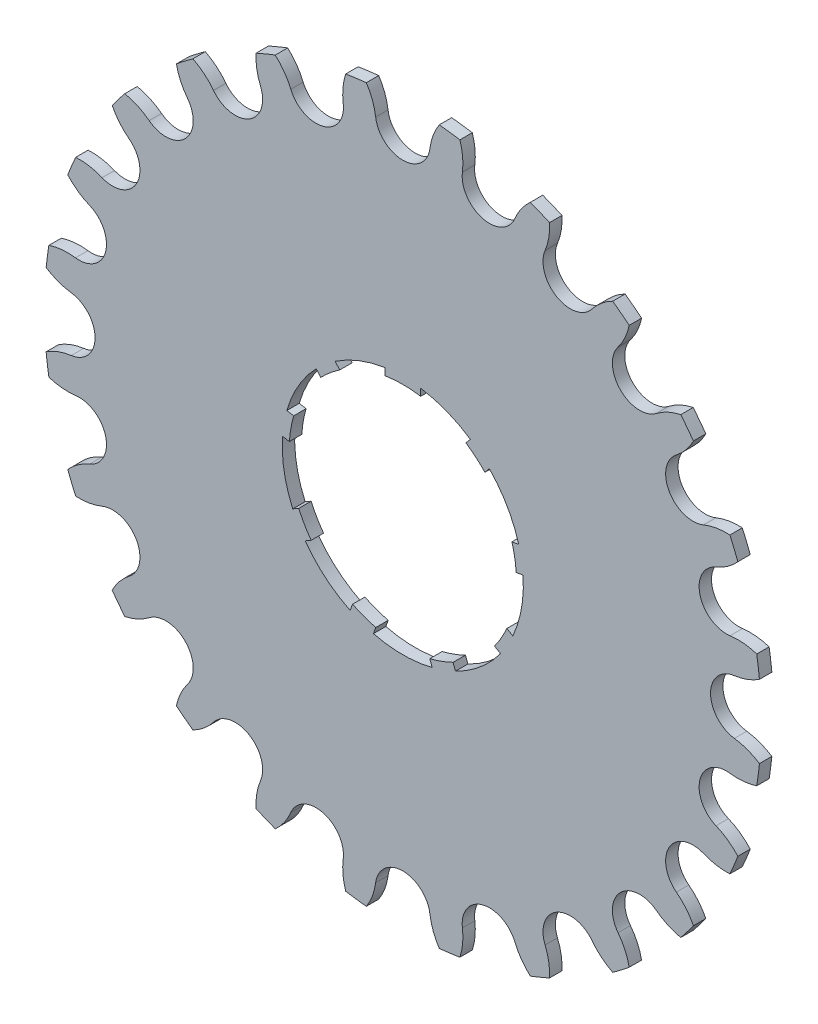
SolidWorks part; units mm, degrees
ref_plane "Alzado" through (0, 0, 0) normal (0, 0, 1) x (1, 0, 0)
ref_plane "Planta" through (0, 0, 0) normal (0, 1, 0) x (1, 0, 0)
ref_plane "Vista lateral" through (0, 0, 0) normal (1, 0, 0) x (0, 0, -1)
sketch "Sk_Disco" plane through (0, 0, 0) normal (0, 0, 1) x (1, 0, 0)
  line L0 (2.6, 17.3058) -> (2.6, 16.2939)
  line L1 (-2.6, 16.2939) -> (-2.6, 17.3058)
  line L2 (-9.8102, 14.4917) -> (-9.1638, 13.7213)
  line L3 (-11.9216, 11.4073) -> (-12.568, 12.1777)
  line L4 (-16.8302, 4.7954) -> (-15.8398, 4.6207)
  line L5 (-16.4649, 1.0754) -> (-17.4553, 1.2501)
  line L6 (-15.9751, -7.1447) -> (-15.1041, -6.6419)
  line L7 (-13.3041, -9.7596) -> (-14.1751, -10.2624)
  line L8 (-7.6451, -15.7418) -> (-7.3011, -14.7968)
  line L9 (-3.9182, -16.028) -> (-4.2622, -16.973)
  line L10 (4.2622, -16.973) -> (3.9182, -16.028)
  line L11 (7.3011, -14.7968) -> (7.6451, -15.7418)
  line L12 (14.1751, -10.2624) -> (13.3041, -9.7596)
  line L13 (15.1041, -6.6419) -> (15.9751, -7.1447)
  line L14 (17.4553, 1.2501) -> (16.4649, 1.0754)
  line L15 (15.8398, 4.6207) -> (16.8302, 4.7954)
  line L16 (12.568, 12.1777) -> (11.9216, 11.4073)
  line L17 (9.1638, 13.7213) -> (9.8102, 14.4917)
  circle A0 centre (0, 0) radius 52.043
  arc A1 (2.6, 16.2939) -> (-2.6, 16.2939) centre (0, 0) ccw
  arc A2 (-2.6, 17.3058) -> (-9.8102, 14.4917) centre (0, 0) ccw
  arc A3 (-9.1638, 13.7213) -> (-11.9216, 11.4073) centre (0, 0) ccw
  arc A4 (-12.568, 12.1777) -> (-16.8302, 4.7954) centre (0, 0) ccw
  arc A5 (-15.8398, 4.6207) -> (-16.4649, 1.0754) centre (0, 0) ccw
  arc A6 (-17.4553, 1.2501) -> (-15.9751, -7.1447) centre (0, 0) ccw
  arc A7 (-15.1041, -6.6419) -> (-13.3041, -9.7596) centre (0, 0) ccw
  arc A8 (-14.1751, -10.2624) -> (-7.6451, -15.7418) centre (0, 0) ccw
  arc A9 (-7.3011, -14.7968) -> (-3.9182, -16.028) centre (0, 0) ccw
  arc A10 (-4.2622, -16.973) -> (4.2622, -16.973) centre (0, 0) ccw
  arc A11 (3.9182, -16.028) -> (7.3011, -14.7968) centre (0, 0) ccw
  arc A12 (7.6451, -15.7418) -> (14.1751, -10.2624) centre (0, 0) ccw
  arc A13 (13.3041, -9.7596) -> (15.1041, -6.6419) centre (0, 0) ccw
  arc A14 (15.9751, -7.1447) -> (17.4553, 1.2501) centre (0, 0) ccw
  arc A15 (16.4649, 1.0754) -> (15.8398, 4.6207) centre (0, 0) ccw
  arc A16 (16.8302, 4.7954) -> (12.568, 12.1777) centre (0, 0) ccw
  arc A17 (11.9216, 11.4073) -> (9.1638, 13.7213) centre (0, 0) ccw
  arc A18 (9.8102, 14.4917) -> (2.6, 17.3058) centre (0, 0) ccw
  dimension "D1" = 104.0861
extrude "Disco" add sketch "Sk_Disco" along normal blind 1.8
sketch "Sk_Hueco" plane through (0, 0, 0) normal (0, 0, 1) x (1, 0, 0)
  line L0 (0, 0) -> (0, 48.6492) construction
  line L1 (0, 0) -> (-12.5913, 46.9916) construction
  line L2 (0, 0) -> (12.5913, 46.9916) construction
  line L3 (0, 48.6492) -> (-12.5913, 46.9916) construction
  line L4 (0, 48.6492) -> (12.5913, 46.9916) construction
  arc A0 (-3.941, 48.1304) -> (3.941, 48.1304) centre (0, 48.6492) ccw
  arc A1 (-3.941, 48.1304) -> (-6.896, 53.6013) centre (-12.5913, 46.9916) ccw
  arc A2 (6.896, 53.6013) -> (3.941, 48.1304) centre (12.5913, 46.9916) ccw
  arc A3 (6.896, 53.6013) -> (-6.896, 53.6013) centre (0, 0) ccw
  dimension "D6" = 3.975
  dimension "D7" = 54.043
  dimension "D1" = 48.6492
  dimension "D2" = 48.6492
  dimension "D3" = 48.6492
  dimension "D4" = 15
  dimension "D5" = 15
extrude "Hueco_diente" cut sketch "Sk_Hueco" along normal through all
ref_axis "Eje_pinon" through (0, 0, -0.09) along (0, 0, 1)
pattern_circular "Matriz_dientes" count 24 over 360 about axis through (0, 0, -0.09) along (0, 0, 1) of "Hueco_diente"
equation "\"Z\"= 24"
equation "\"p\"= 12.7"
equation "\"Dr\"= 7.75"
equation "\"e\"= 1.8"
equation "\"D\"= \"p\" / sin ( 180 / \"Z\" )"
equation "\"De\"= \"p\" * ( 0.6 + 1 / tan ( 180 / \"Z\" ) )"
equation "\"Di\"= \"D\" - \"Dr\""
equation "\"Ang\"= 360 / \"Z\""
equation "\"D1@Sk_Disco\" = \"De\""
equation "\"D1@Disco\" = \"e\""
equation "\"D1@Sk_Hueco\" = \"D\" / 2"
equation "\"D2@Sk_Hueco\" = \"D\" / 2"
equation "\"D3@Sk_Hueco\" = \"D\" / 2"
equation "\"D4@Sk_Hueco\" = \"Ang\""
equation "\"D5@Sk_Hueco\" = \"Ang\""
equation "\"D6@Sk_Hueco\" = \"Dr\" / 2 + 0.1"
equation "\"D7@Sk_Hueco\" = \"De\" / 2 + 2"
equation "\"D1@Matriz_dientes\" = \"Z\""
